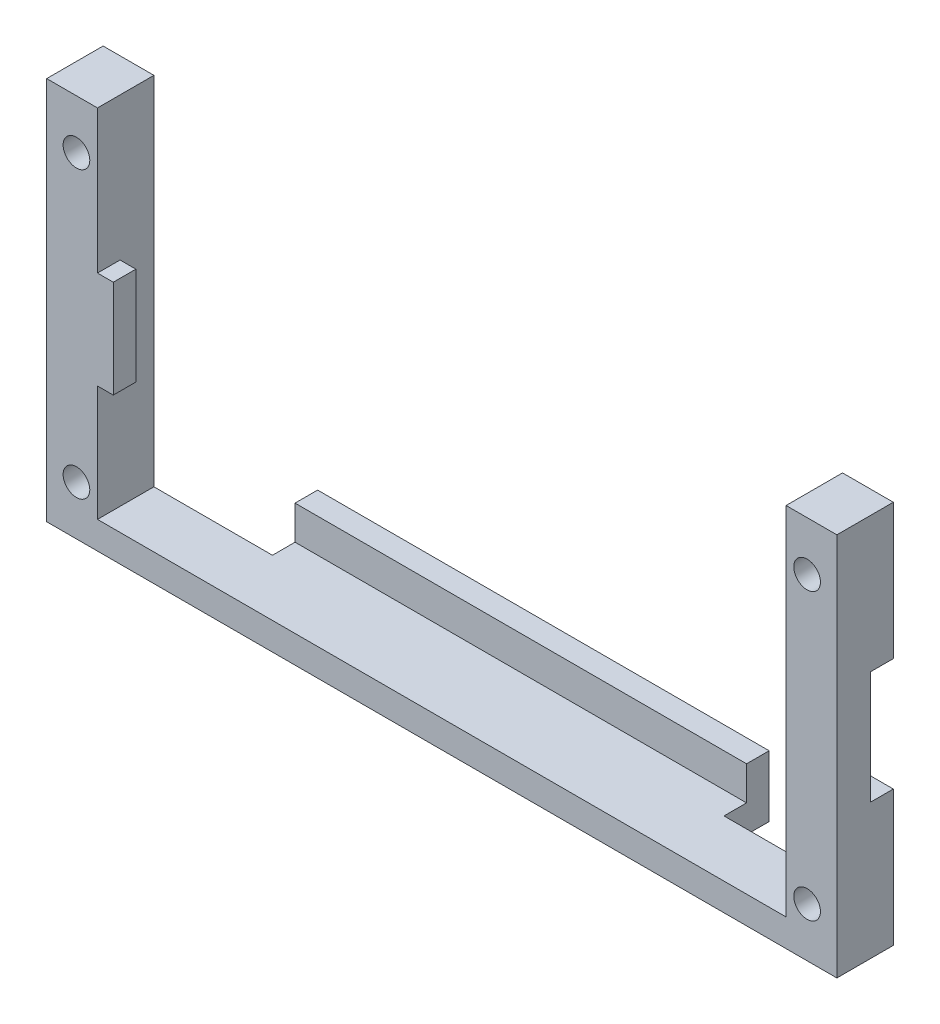
SolidWorks part; units mm, degrees
ref_plane "Front Plane" through (0, 0, 0) normal (0, 0, 1) x (1, 0, 0)
ref_plane "Top Plane" through (0, 0, 0) normal (0, 1, 0) x (1, 0, 0)
ref_plane "Right Plane" through (0, 0, 0) normal (1, 0, 0) x (0, 0, -1)
sketch "Sketch1" plane through (0, 0, 0) normal (0, 0, 1) x (1, 0, 0)
  line L1 (-44.45, 21.59) -> (44.45, 21.59)
  line L2 (-44.45, 21.59) -> (-44.45, -21.59)
  line L3 (-44.45, -21.59) -> (44.45, -21.59)
  line L4 (44.45, 21.59) -> (44.45, -21.59)
  line L5 (-38.735, 18.5) -> (38.735, 18.5)
  line L6 (-38.735, 18.5) -> (-38.735, -18.5)
  line L7 (-38.735, -18.5) -> (38.735, -18.5)
  line L8 (38.735, 18.5) -> (38.735, -18.5)
  point P4 (0, 21.59)
  point P5 (-44.45, 0)
  point P11 (0, 18.5)
  point P12 (-38.735, 0)
  dimension "D1" = 88.9
  dimension "D2" = 43.18
  dimension "D3" = 77.47
  dimension "D4" = 37
extrude "Boss-Extrude1" add sketch "Sketch1" along normal blind 6.35
sketch "Sketch2" plane through (0, 0, 6.35) normal (0, 0, 1) x (1, 0, 0)
  line L2 (0, -55) -> (0, 55) construction
  line L4 (55, 0) -> (-55, 0) construction
  circle A1 centre (41.1, 16.05) radius 1.5
  circle A2 centre (-41.1, 16.05) radius 1.5
  circle A3 centre (-41.1, -16.05) radius 1.5
  circle A4 centre (41.1, -16.05) radius 1.5
  dimension "D1" = 82.2
  dimension "D3" = 3
  dimension "D2" = 32.1
extrude "Cut-Extrude1" cut sketch "Sketch2" against normal blind 10.16
sketch "Sketch4" plane through (-38.735, 0, 0) normal (1, 0, 0) x (0, 0, -1)
  line L0 (-6.35, -21.59) -> (-6.35, 21.59) construction
  line L1 (-6.35, 5.5) -> (-3.81, 5.5)
  line L2 (-6.35, 5.5) -> (-6.35, -5.5)
  line L3 (-6.35, -5.5) -> (-3.81, -5.5)
  line L4 (-3.81, 5.5) -> (-3.81, -5.5)
  point P6 (-3.81, 0)
  dimension "D1" = 11
  dimension "D2" = 2.54
extrude "Boss-Extrude3" add sketch "Sketch4" along normal blind 1.778
sketch "Sketch5" plane through (0, 0, 0) normal (0, 0, -1) x (-1, 0, 0)
  line L0 (-44.45, 21.59) -> (44.45, 21.59) construction
  line L1 (-38.735, 21.59) -> (38.735, 21.59)
  line L2 (-38.735, 21.59) -> (-38.735, 18.5)
  line L3 (-38.735, 18.5) -> (38.735, 18.5)
  line L4 (38.735, 21.59) -> (38.735, 18.5)
extrude "Cut-Extrude2" cut sketch "Sketch5" against normal through all
sketch "Sketch6" plane through (0, 0, 0) normal (0, 0, -1) x (-1, 0, 0)
  line L0 (38.735, -18.5) -> (-38.735, -18.5) construction
  line L1 (-25.4, -18.5) -> (25.4, -18.5)
  line L2 (-25.4, -18.5) -> (-25.4, -21.59)
  line L3 (-25.4, -21.59) -> (25.4, -21.59)
  line L4 (25.4, -18.5) -> (25.4, -21.59)
  line L5 (44.45, -21.59) -> (-44.45, -21.59) construction
  point P8 (0, -18.5)
  dimension "D1" = 50.8
extrude "Boss-Extrude4" add sketch "Sketch6" along normal blind 5.08
sketch "Sketch7" plane through (0, -18.5, 0) normal (0, 1, 0) x (1, 0, 0)
  line L1 (-25.4, 5.08) -> (25.4, 5.08)
  line L2 (-25.4, 5.08) -> (-25.4, 2.54)
  line L3 (-25.4, 2.54) -> (25.4, 2.54)
  line L4 (25.4, 5.08) -> (25.4, 2.54)
  dimension "D1" = 2.54
extrude "Boss-Extrude5" add sketch "Sketch7" along normal blind 3.81
sketch "Sketch8" plane through (38.735, 0, 0) normal (-1, 0, 0) x (0, 0, 1)
  line L1 (0, 6.35) -> (2.54, 6.35)
  line L2 (0, 6.35) -> (0, -6.35)
  line L3 (0, -6.35) -> (2.54, -6.35)
  line L4 (2.54, 6.35) -> (2.54, -6.35)
  line L7 (0, 21.59) -> (0, -21.59) construction
  point P4 (0, 0)
  dimension "D1" = 2.54
  dimension "D2" = 12.7
extrude "Cut-Extrude3" cut sketch "Sketch8" against normal through all
